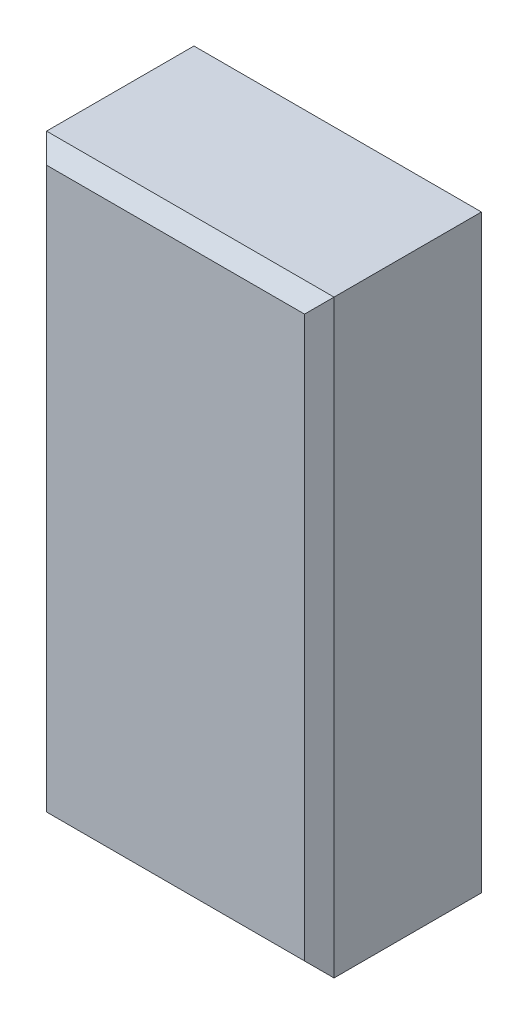
SolidWorks part; units mm, degrees
ref_plane "Front Plane" through (0, 0, 0) normal (0, 0, 1) x (1, 0, 0)
ref_plane "Top Plane" through (0, 0, 0) normal (0, 1, 0) x (1, 0, 0)
ref_plane "Right Plane" through (0, 0, 0) normal (1, 0, 0) x (0, 0, -1)
sketch "Sketch1" plane through (0, 0, 0) normal (0, 0, 1) x (1, 0, 0)
  line L1 (-9.75, 20) -> (9.75, 20)
  line L2 (-9.75, 20) -> (-9.75, -20)
  line L3 (-9.75, -20) -> (9.75, -20)
  line L4 (9.75, 20) -> (9.75, -20)
  line L5 (-9.75, 20) -> (9.75, -20) construction
  line L6 (-9.75, -20) -> (9.75, 20) construction
  point P0 (0, 0)
  dimension "D1" = 19.5
  dimension "D2" = 40
extrude "Boss-Extrude1" add sketch "Sketch1" along normal blind 11
chamfer "Chamfer1" distance 1 angle 45 4 edges at (0, -20, 11) (-9.75, 0, 11) (0, 20, 11) (9.75, 0, 11)
equation "\"thiccnes\"=9.5"
equation "\"D1@Boss-Extrude1\"=\"thiccnes\""
